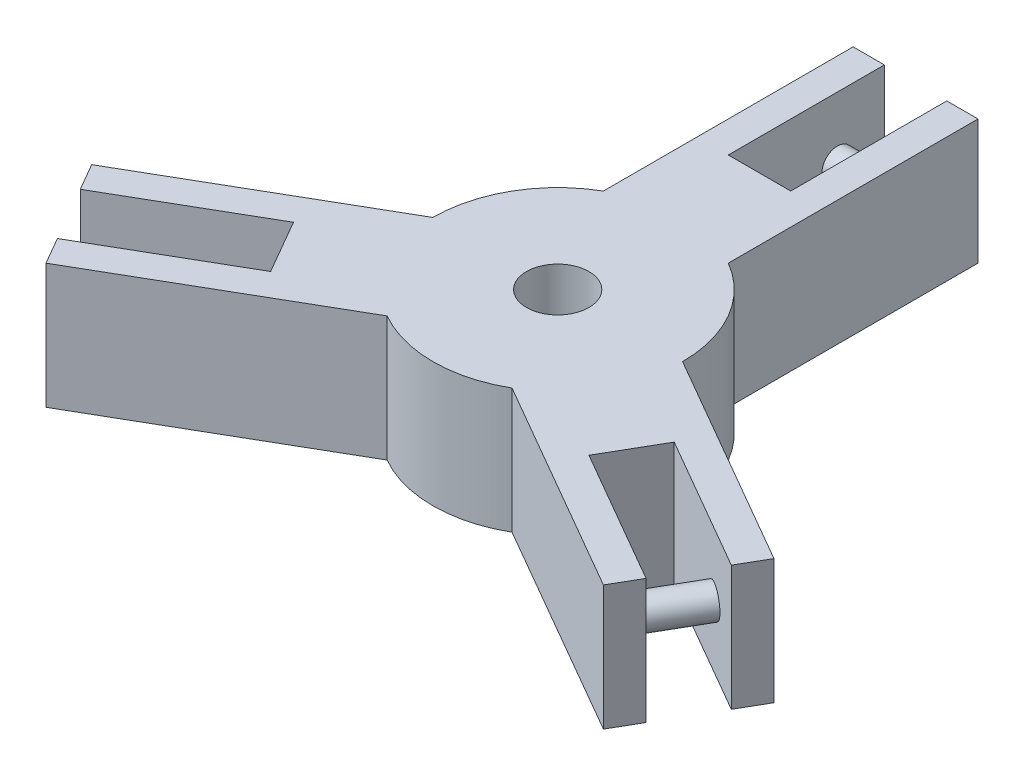
SolidWorks part; units mm, degrees
material "AISI 1020"
ref_plane "Front Plane" through (0, 0, 0) normal (0, 0, 1) x (1, 0, 0)
ref_plane "Top Plane" through (0, 0, 0) normal (0, 1, 0) x (1, 0, 0)
ref_plane "Right Plane" through (0, 0, 0) normal (1, 0, 0) x (0, 0, -1)
sketch "Sketch1" plane through (0, 0, 0) normal (0, 1, 0) x (1, 0, 0)
  line L1 (-20, 114.641) -> (-20, 34.641)
  line L2 (-20, 114.641) -> (-10, 114.641)
  line L3 (109.282, -40) -> (40, 0)
  line L4 (10, 114.641) -> (20, 114.641)
  line L5 (20, 114.641) -> (20, 34.641)
  line L6 (109.282, -40) -> (104.282, -48.6603)
  line L7 (10, 114.641) -> (10, 64.641)
  line L8 (10, 64.641) -> (-10, 64.641)
  line L9 (-10, 114.641) -> (-10, 64.641)
  line L10 (94.282, -65.9808) -> (89.282, -74.641)
  line L11 (89.282, -74.641) -> (20, -34.641)
  line L12 (94.282, -65.9808) -> (50.9808, -40.9808)
  line L13 (50.9808, -40.9808) -> (60.9808, -23.6603)
  line L14 (104.282, -48.6603) -> (60.9808, -23.6603)
  line L15 (-89.282, -74.641) -> (-20, -34.641)
  line L16 (-89.282, -74.641) -> (-94.282, -65.9808)
  line L17 (-104.282, -48.6603) -> (-109.282, -40)
  line L18 (-109.282, -40) -> (-40, 0)
  line L19 (-104.282, -48.6603) -> (-60.9808, -23.6603)
  line L20 (-60.9808, -23.6603) -> (-50.9808, -40.9808)
  line L21 (-94.282, -65.9808) -> (-50.9808, -40.9808)
  circle A0 centre (0, 0) radius 10
  circle A1 centre (0, 0) radius 40
  dimension "D1" = 80
  dimension "D2" = 20
  dimension "D3" = 20
  dimension "D4" = 40
  dimension "D5" = 80
  dimension "D6" = 50
  dimension "D7" = 3
extrude "Boss-Extrude1" add sketch "Sketch1" along normal blind 40 contours A1 L18 L17 L19 L20 L21 L16 L15 | A1 L5 L4 L7 L8 L9 L2 L1 | A1 | A1 L11 L10 L12 L13 L14 L6 L3 region at (-15, 0, -113.7466) region at (0, 0, -38.8686) region at (-35.6488, 0, 20.5819) region at (74.0592, 0, 21.0078)
sketch "Sketch2" plane through (-10, 0, 0) normal (1, 0, 0) x (0, 0, -1)
  line L0 (114.641, 20) -> (99.641, 20) construction
  line L1 (114.641, 40) -> (114.641, 0) construction
  circle A0 centre (99.641, 20) radius 5
  dimension "D2" = 10
  dimension "D1" = 15
extrude "Boss-Extrude2" add sketch "Sketch2" along normal blind 25
pattern_circular "CirPattern1" count 3 over 360 about axis through (0, 40, 0) along (0, 1, 0) of "Boss-Extrude2"
